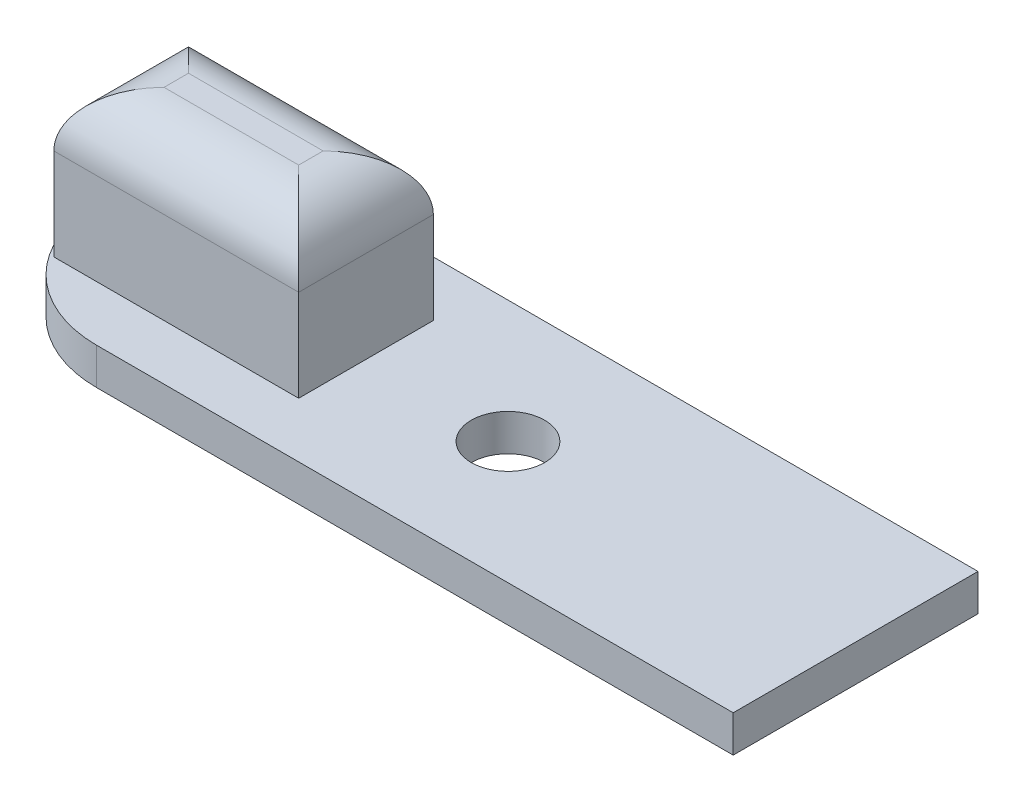
SolidWorks part; units mm, degrees
ref_plane "Front Plane" through (0, 0, 0) normal (0, 0, 1) x (1, 0, 0)
ref_plane "Top Plane" through (0, 0, 0) normal (0, 1, 0) x (1, 0, 0)
ref_plane "Right Plane" through (0, 0, 0) normal (1, 0, 0) x (0, 0, -1)
sketch "Sketch1" plane through (0, 0, 0) normal (0, 1, 0) x (1, 0, 0)
  line L1 (-31, 10) -> (0, 10)
  line L2 (-31, 10) -> (-31, 0)
  line L3 (-31, 0) -> (0, 0)
  line L4 (0, 10) -> (0, 0)
  dimension "D1" = 31
  dimension "D2" = 10
extrude "Boss-Extrude1" add sketch "Sketch1" along normal blind 1.5
sketch "Sketch2" plane through (0, 1.5, 0) normal (0, 1, 0) x (1, 0, 0)
  line L0 (0, 0) -> (0, 10) construction
  line L1 (0, 10) -> (-31, 10) construction
  circle A0 centre (-14.2, 5) radius 1.5
  dimension "D1" = 3
  dimension "D2" = 14.2
  dimension "D3" = 5
extrude "Cut-Extrude1" cut sketch "Sketch2" against normal up to next
sketch "Sketch3" plane through (0, 1.5, 0) normal (0, 1, 0) x (1, 0, 0)
  line L0 (0, 10) -> (-31, 10) construction
  line L1 (-30, 2.25) -> (-20, 2.25)
  line L2 (-30, 2.25) -> (-30, 7.75)
  line L3 (-30, 7.75) -> (-20, 7.75)
  line L4 (-20, 2.25) -> (-20, 7.75)
  line L5 (-31, 10) -> (-31, 0) construction
  dimension "D1" = 10
  dimension "D2" = 5.5
  dimension "D3" = 2.25
  dimension "D4" = 1
extrude "Boss-Extrude2" add sketch "Sketch3" along normal blind 6
fillet "Fillet3" radius 2.25 4 edges at (-25, 7.5, -7.75) (-20, 7.5, -5) (-25, 7.5, -2.25) (-30, 7.5, -5)
fillet "Fillet4" radius 5 2 edges at (-31, 0.75, 0) (-31, 0.75, -10)
